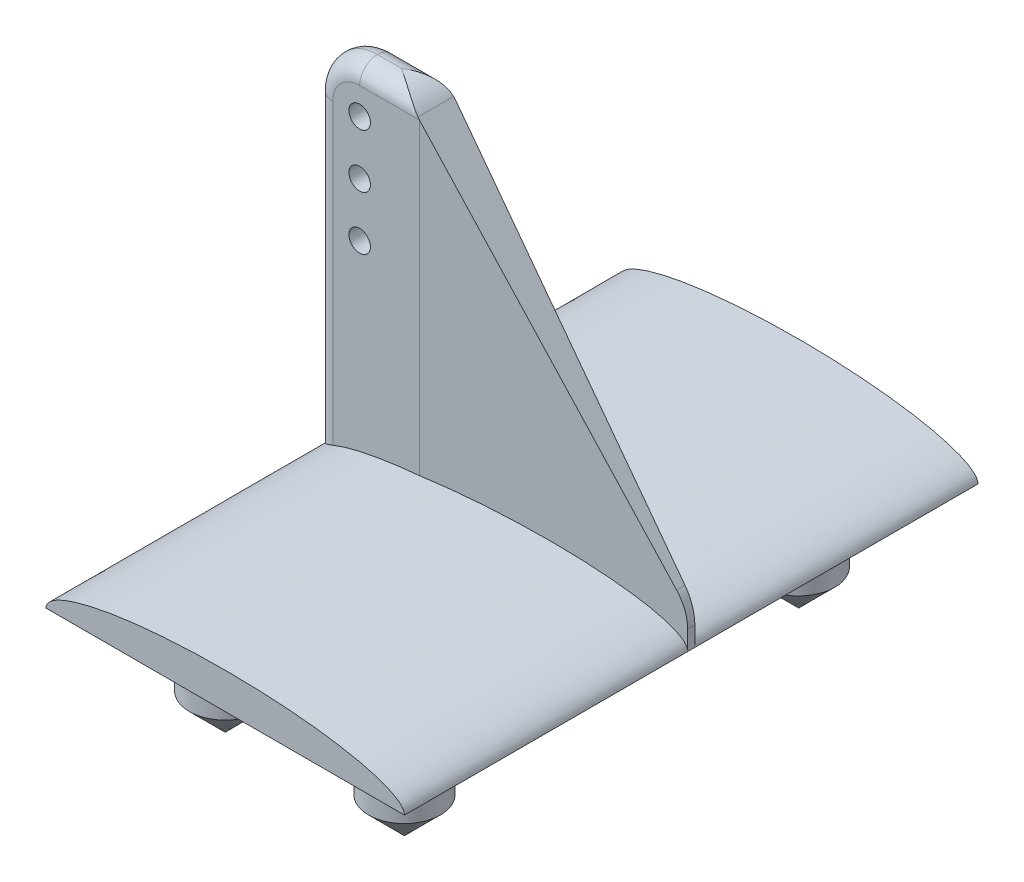
SolidWorks part; units mm, degrees
ref_plane "Front Plane" through (0, 0, 0) normal (0, 0, 1) x (1, 0, 0)
ref_plane "Top Plane" through (0, 0, 0) normal (0, 1, 0) x (1, 0, 0)
ref_plane "Right Plane" through (0, 0, 0) normal (1, 0, 0) x (0, 0, -1)
sketch "Sketch1" plane through (0, 0, 0) normal (0, 0, 1) x (1, 0, 0)
  line L0 (0, 0) -> (0, 18)
  line L1 (0, 18) -> (5, 18)
  line L2 (5, 18) -> (20, 0)
  line L3 (20, 0) -> (0, 0)
  line L4 (0, 0) -> (0, -2)
  line L5 (0, -2) -> (20, -2)
  line L6 (20, -2) -> (20, 0)
  circle A0 centre (2.5, 15.5) radius 0.6
  circle A1 centre (2.5, 12.5) radius 0.6
  circle A2 centre (2.5, 9.5) radius 0.6
  dimension "D1" = 1.2
  dimension "D2" = 18
  dimension "D3" = 5
  dimension "D4" = 2.5
  dimension "D5" = 20
  dimension "D6" = 2.5
  dimension "D7" = 3
  dimension "D8" = 3
  dimension "D9" = 2
extrude "Boss-Extrude1" add sketch "Sketch1" along normal blind 2 contours L3 L2 L1 L0 A2 A1 A0 | L5 L6 L3 L4
fillet "Fillet1" radius 2.5 3 edges at (5, 18, 1) (0, 18, 1) (20, 0, 1)
fillet "Fillet2" radius 1 6 edges at (0, 6.75, 2) (0, 6.75, 0) (3.1645, 18, 2) (3.1645, 18, 0) (0.7322, 17.2678, 2) (0.7322, 17.2678, 0)
sketch "Sketch4" plane through (0, -2, 0) normal (0, -1, 0) x (1, 0, 0)
  line L0 (5.8333, 2) -> (2.5, 2) construction
  line L1 (5.8333, 2) -> (2.5, 2)
  line L2 (5.8333, 2) -> (20, 1.2)
  line L3 (20, 2) -> (20, 0) construction
  line L4 (20, 1.2) -> (20, 0.8)
  line L5 (20, 0.8) -> (5.8333, 0)
  dimension "D1" = 0.4
  dimension "D2" = 0.8
extrude "Cut-Extrude1" cut sketch "Sketch4" against normal through all and the other way through all
sketch "Sketch3" plane through (0, 0, 0) normal (0, 0, -1) x (-1, 0, 0)
  line L0 (-1, -2) -> (-5.8333, -2) construction
  line L2 (-1, -2) -> (-5.8333, -2)
  line L3 (-20, 0) -> (0, 0)
  line L4 (-20, -2) -> (0, -2)
  ellipse E0 centre (-10, -2) end of major axis (-20, -2) minor radius 2 (0, -2) -> (-20, -2) ccw
  line M9 (-5.8333, -2) -> (-1, -2)
  line M15 (-1, -2) -> (-1, 15.5)
  line M16 (-5.8333, 17) -> (-5.8333, -2)
extrude "Boss-Extrude2" add sketch "Sketch3" along normal blind 15 and the other way blind 17 contours E0 L4 M16 | E0 M15 M16 M9 | L4 E0 M15
sketch "Sketch5" plane through (0, -2, 0) normal (0, -1, 0) x (1, 0, 0)
  line L1 (0, 17) -> (0, 1) construction
  line L2 (20, 17) -> (0, 17) construction
  line L3 (20, -15) -> (0, -15) construction
  circle A0 centre (5, 12) radius 2
  circle A1 centre (15, 12) radius 2
  circle A2 centre (15, -10) radius 2
  circle A3 centre (5, -10) radius 2
  point P14 (0, 0)
  point P15 (0, 0)
  point P16 (0, 0)
  point P17 (14.8442, 10.2414)
  point P18 (0, 0)
  dimension "D4" = 4
  dimension "D5" = 5
  dimension "D6" = 10
  dimension "D7" = 5
  dimension "D8" = 5
extrude "Boss-Extrude3" add sketch "Sketch5" along normal blind 6
chamfer "Chamfer1" distance 2 angle 45 4 edges at (15, -8, 10) (5, -8, 10) (15, -8, -12) (5, -8, -12)
